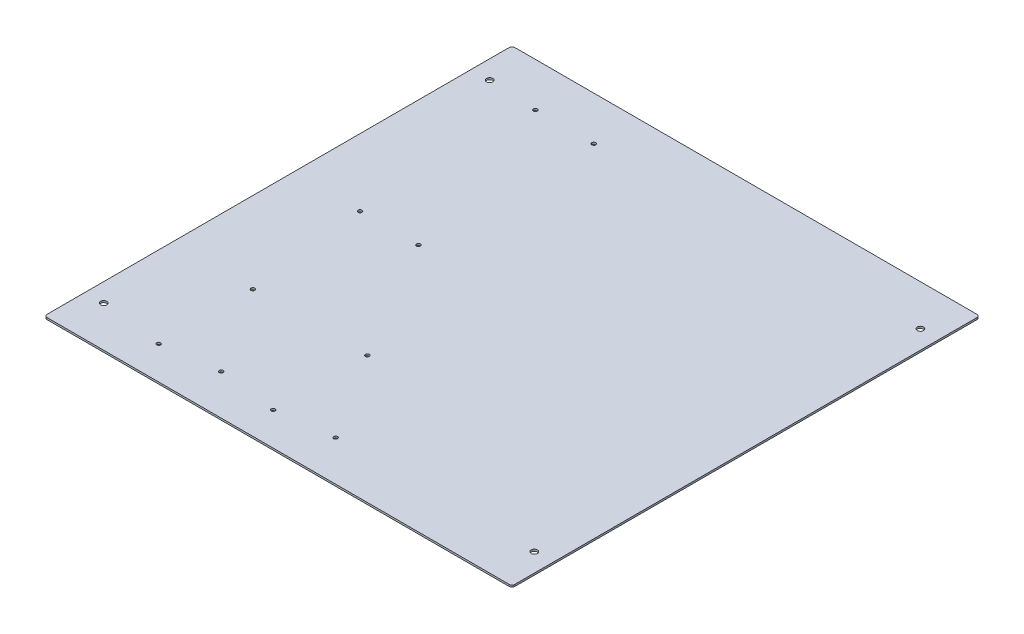
SolidWorks part; units mm, degrees
ref_plane "Front Plane" through (0, 0, 0) normal (0, 0, 1) x (1, 0, 0)
ref_plane "Top Plane" through (0, 0, 0) normal (0, 1, 0) x (1, 0, 0)
ref_plane "Right Plane" through (0, 0, 0) normal (1, 0, 0) x (0, 0, -1)
sketch "Sketch1" plane through (0, 0, 0) normal (0, 1, 0) x (1, 0, 0)
  line L1 (-200.025, 200.025) -> (200.025, 200.025)
  line L2 (-200.025, 200.025) -> (-200.025, -200.025)
  line L3 (-200.025, -200.025) -> (200.025, -200.025)
  line L4 (200.025, 200.025) -> (200.025, -200.025)
  line L5 (-200.025, 200.025) -> (200.025, -200.025) construction
  line L6 (-200.025, -200.025) -> (200.025, 200.025) construction
  point P0 (0, 0)
  dimension "D1" = 400.05
  dimension "D2" = 400.05
extrude "Boss-Extrude1" add sketch "Sketch1" along normal blind 1.5875
sketch "Sketch2" plane through (0, 1.5875, 0) normal (0, 1, 0) x (1, 0, 0)
  line L0 (-203.2, 0) -> (203.2, 0) construction
  line L1 (-203.2, 203.2) -> (203.2, 203.2) construction
  line L2 (-203.2, 203.2) -> (-203.2, -203.2) construction
  line L3 (-203.2, -203.2) -> (203.2, -203.2) construction
  line L4 (203.2, 203.2) -> (203.2, -203.2) construction
  line L5 (-203.2, 203.2) -> (203.2, -203.2) construction
  line L6 (-203.2, -203.2) -> (203.2, 203.2) construction
  line L7 (0, 203.2) -> (0, -203.2) construction
  circle A0 centre (-184.15, -165.1) radius 2.665
  circle A1 centre (184.15, -165.1) radius 2.665
  circle A2 centre (184.15, 165.1) radius 2.665
  circle A3 centre (-184.15, 165.1) radius 2.665
  point P0 (0, 0)
  dimension "D2" = 19.05
  dimension "D3" = 38.1
  dimension "D4" = 5.33
  dimension "D1" = 406.4
extrude "Cut-Extrude1" cut sketch "Sketch2" against normal up to next
fillet "Fillet1" radius 2.54 4 edges at (-200.025, 0.7937, -200.025) (200.025, 0.7937, -200.025) (200.025, 0.7937, 200.025) (-200.025, 0.7937, 200.025)
sketch "Sketch3" plane through (0, 0, 0) normal (0, -1, 0) x (1, 0, 0)
  circle A0 centre (-130.4397, 171.7662) radius 1.665
  circle A1 centre (-83.1864, 165.5581) radius 1.665
  circle A2 centre (-130.5674, 91.046) radius 1.665
  circle A3 centre (-32.5002, 171.7662) radius 1.665
  circle A4 centre (14.753, 165.5581) radius 1.665
  circle A5 centre (-32.628, 91.046) radius 1.665
  dimension "D1" = 3.33
extrude "Cut-Extrude2" cut sketch "Sketch3" against normal up to next
sketch "Sketch4" plane through (0, 1.5875, 0) normal (0, 1, 0) x (1, 0, 0)
  circle A0 centre (-92.525, 12.525) radius 1.1727 construction
  circle A1 centre (-142.525, 12.525) radius 1.1727 construction
  circle A2 centre (-92.525, 162.525) radius 1.1727 construction
  circle A3 centre (-142.525, 162.525) radius 1.1727 construction
  circle A4 centre (-92.525, 12.525) radius 1.1727 construction
  circle A5 centre (-142.525, 12.525) radius 1.1727 construction
  circle A6 centre (-92.525, 162.525) radius 1.1727 construction
  circle A7 centre (-142.525, 162.525) radius 1.1727 construction
  circle A8 centre (-142.525, 162.525) radius 1.665
  circle A9 centre (-92.525, 162.525) radius 1.665
  circle A10 centre (-92.525, 12.525) radius 1.665
  circle A11 centre (-142.525, 12.525) radius 1.665
  dimension "D1" = 3.33
extrude "Cut-Extrude3" cut sketch "Sketch4" against normal up to next
